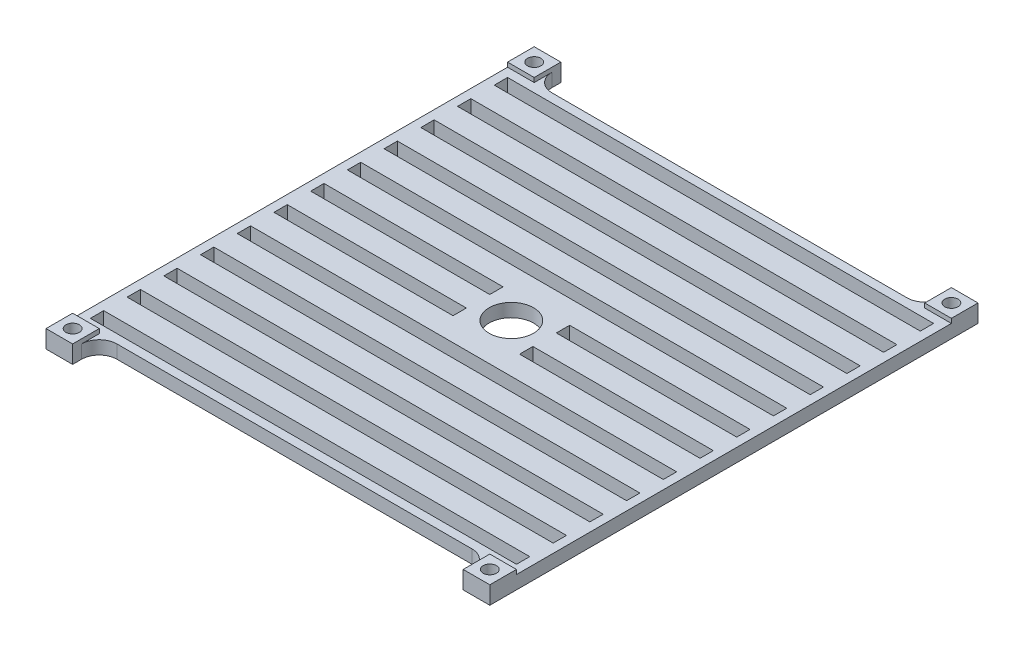
SolidWorks part; units mm, degrees
ref_plane "Front Plane" through (0, 0, 0) normal (0, 0, 1) x (1, 0, 0)
ref_plane "Top Plane" through (0, 0, 0) normal (0, 1, 0) x (1, 0, 0)
ref_plane "Right Plane" through (0, 0, 0) normal (1, 0, 0) x (0, 0, -1)
sketch "Sketch1" plane through (0, 0, 0) normal (0, 1, 0) x (1, 0, 0)
  line L0 (-48, -35.7273) -> (48, -35.7273)
  line L1 (50, 49) -> (-50, 49)
  line L2 (50, 49) -> (50, -49)
  line L3 (50, -49) -> (-50, -49)
  line L4 (-50, 49) -> (-50, -49)
  line L5 (-48, -38.7273) -> (48, -38.7273)
  line L6 (50, -49) -> (-50, 49) construction
  line L7 (-48, -44) -> (48, -44)
  line L8 (-48, -44) -> (-48, -47)
  line L9 (-48, -47) -> (48, -47)
  line L10 (48, -44) -> (48, -47)
  line L11 (-48, -35.7273) -> (-48, -38.7273)
  line L12 (48, -35.7273) -> (48, -38.7273)
  line L13 (-48, -27.4545) -> (48, -27.4545)
  line L14 (-48, -30.4545) -> (48, -30.4545)
  line L15 (-48, -27.4545) -> (-48, -30.4545)
  line L16 (48, -27.4545) -> (48, -30.4545)
  line L17 (-48, -19.1818) -> (48, -19.1818)
  line L18 (-48, -22.1818) -> (48, -22.1818)
  line L19 (-48, -19.1818) -> (-48, -22.1818)
  line L20 (48, -19.1818) -> (48, -22.1818)
  line L21 (-48, -10.9091) -> (48, -10.9091)
  line L22 (-48, -13.9091) -> (48, -13.9091)
  line L23 (-48, -10.9091) -> (-48, -13.9091)
  line L24 (48, -10.9091) -> (48, -13.9091)
  line L25 (-48, -2.6364) -> (48, -2.6364)
  line L26 (-48, -5.6364) -> (48, -5.6364)
  line L27 (-48, -2.6364) -> (-48, -5.6364)
  line L28 (48, -2.6364) -> (48, -5.6364)
  line L29 (-48, 5.6364) -> (48, 5.6364)
  line L30 (-48, 2.6364) -> (48, 2.6364)
  line L31 (-48, 5.6364) -> (-48, 2.6364)
  line L32 (48, 5.6364) -> (48, 2.6364)
  line L33 (-48, 13.9091) -> (48, 13.9091)
  line L34 (-48, 10.9091) -> (48, 10.9091)
  line L35 (-50, -49) -> (-44, -49)
  line L36 (-50, -49) -> (-50, -55)
  line L37 (-50, -55) -> (-44, -55)
  line L38 (-44, -49) -> (-44, -55)
  line L39 (-47, -55) -> (-47, -23.3895) construction
  line L40 (-44, -52) -> (-28.5191, -52) construction
  line L41 (44, -52) -> (28.5191, -52) construction
  line L42 (47, -55) -> (47, -23.3895) construction
  line L43 (44, -49) -> (44, -55)
  line L44 (50, -55) -> (44, -55)
  line L45 (50, -49) -> (50, -55)
  line L46 (-0.152, 0) -> (57.0928, 0) construction
  line L47 (47, 55) -> (47, 23.3895) construction
  line L48 (44, 52) -> (28.5191, 52) construction
  line L49 (-44, 52) -> (-28.5191, 52) construction
  line L50 (-47, 55) -> (-47, 23.3895) construction
  line L51 (50, 49) -> (50, 55)
  line L52 (50, 55) -> (44, 55)
  line L53 (44, 49) -> (44, 55)
  line L54 (-44, 49) -> (-44, 55)
  line L55 (-50, 55) -> (-44, 55)
  line L56 (-50, 49) -> (-50, 55)
  line L57 (-48, 13.9091) -> (-48, 10.9091)
  line L58 (48, 13.9091) -> (48, 10.9091)
  line L59 (-48, 22.1818) -> (48, 22.1818)
  line L60 (-48, 19.1818) -> (48, 19.1818)
  line L61 (-48, 22.1818) -> (-48, 19.1818)
  line L62 (48, 22.1818) -> (48, 19.1818)
  line L63 (-48, 30.4545) -> (48, 30.4545)
  line L64 (-48, 27.4545) -> (48, 27.4545)
  line L65 (-48, 30.4545) -> (-48, 27.4545)
  line L66 (48, 30.4545) -> (48, 27.4545)
  line L67 (-48, 38.7273) -> (48, 38.7273)
  line L68 (-48, 35.7273) -> (48, 35.7273)
  line L69 (-48, 38.7273) -> (-48, 35.7273)
  line L70 (48, 38.7273) -> (48, 35.7273)
  line L71 (-48, 47) -> (48, 47)
  line L72 (-48, 44) -> (48, 44)
  line L73 (-48, 47) -> (-48, 44)
  line L74 (48, 47) -> (48, 44)
  line L76 (7.348, 5.6364) -> (-7.652, 5.6364)
  line L77 (7.348, 5.6364) -> (7.348, -5.6364)
  line L78 (7.348, -5.6364) -> (-7.652, -5.6364)
  line L79 (-7.652, 5.6364) -> (-7.652, -5.6364)
  line L80 (7.348, 5.6364) -> (-7.652, -5.6364) construction
  line L81 (7.348, -5.6364) -> (-7.652, 5.6364) construction
  circle A0 centre (-0.152, 0) radius 5
  circle A1 centre (-47, -52) radius 1.5
  circle A2 centre (47, -52) radius 1.5
  circle A3 centre (47, 52) radius 1.5
  circle A4 centre (-47, 52) radius 1.5
  point P0 (0, 0)
  dimension "D3" = 10
  dimension "D4" = 12
  dimension "D5" = 2
  dimension "D6" = 15
  dimension "D22" = 3
  dimension "D8" = 2
  dimension "D9" = 2
  dimension "D10" = 2
  dimension "D11" = 3
  dimension "D19" = 100
  dimension "D20" = 6
  dimension "D21" = 6
extrude "Boss-Extrude4" add sketch "Sketch1" along normal blind 3 contours L1 L4 L3 L2 L79 L30 L31 L29 L32 L77 L25 L28 L26 L27 L7 L10 L9 L8 L0 L12 L5 L11 L13 L16 L14 L15 L17 L20 L18 L19 L21 L24 L22 L23 | A0 L25 L79 L26 L77 | A0 L30 L79 L25 | A0 L30 L77 L29 L79 | A0 L25 L77 L30 region at (48.5999, 0, 0) region at (-6.2719, 0, 0) region at (-6.0263, 0, 2.7893) region at (-7.4991, 0, -4.1364) region at (5.9678, 0, 0)
extrude "Boss-Extrude6" add sketch "Sketch1<8>" along normal blind 4 contours L38 L3 L36 L37 A1 | L45 L3 L43 L44 A2 | L53 L1 L51 L52 A3 | L56 L1 L54 L55 A4 region at (47, 0, -49.0849) region at (49.9151, 0, 52) region at (-47, 0, -49.0849) region at (-44.0849, 0, 52)
sketch "Sketch1<8>" plane through (0, 0, 0) normal (0, 1, 0) x (1, 0, 0) same geometry as "Sketch1"
fillet "Fillet3" radius 4 4 edges at (44, 1.5, -49) (-44, 1.5, -49) (-44, 1.5, 49) (44, 1.5, 49)
